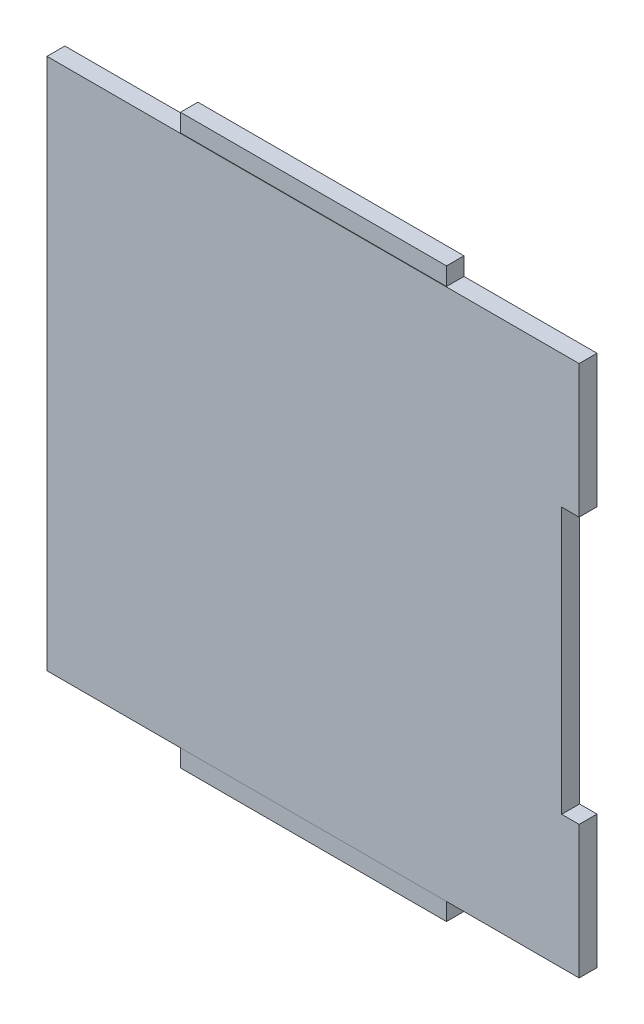
SolidWorks part; units mm, degrees
ref_plane "Front Plane" through (0, 0, 0) normal (0, 0, 1) x (1, 0, 0)
ref_plane "Top Plane" through (0, 0, 0) normal (0, 1, 0) x (1, 0, 0)
ref_plane "Right Plane" through (0, 0, 0) normal (1, 0, 0) x (0, 0, -1)
sketch "Sketch1" plane through (0, 0, 0) normal (0, 0, 1) x (1, 0, 0)
  line L1 (-50, 50) -> (50, 50)
  line L2 (-50, 50) -> (-50, -50)
  line L3 (-50, -50) -> (50, -50)
  line L4 (50, 50) -> (50, -50)
  line L5 (-50, 50) -> (50, -50) construction
  line L6 (-50, -50) -> (50, 50) construction
  point P0 (0, 0)
  dimension "D1" = 100
  dimension "D2" = 100
extrude "Boss-Extrude1" add sketch "Sketch1" along normal blind 3.36
sketch "Sketch2" [suppressed] plane through (0, 0, 3.36) normal (0, 0, 1) x (1, 0, 0)
  line L0 (50, 50) -> (-50, 50) construction
  line L1 (-25, 50) -> (25, 50)
  line L2 (-25, 50) -> (-25, 53.36)
  line L3 (-25, 53.36) -> (25, 53.36)
  line L4 (25, 50) -> (25, 53.36)
  line L5 (0, 0) -> (0, 53.36) construction
  line L6 (0, 0) -> (50, 0) construction
  line L7 (50, -50) -> (50, 50) construction
  dimension "D1" = 3.36
  dimension "D2" = 50
extrude "Boss-Extrude2" [suppressed] add sketch "Sketch2" against normal up to vertex up to point (-50, 50, 0)
mirror "Mirror1" [suppressed] about plane through (0, 0, 0) normal (0, 1, 0)
sketch "Sketch5" [suppressed] plane through (0, 0, 0) normal (0, 0, -1) x (-1, 0, 0)
  line L0 (0, 0) -> (-50, 0) construction
  line L1 (-50, -50) -> (-50, 50) construction
  line L2 (0, 0) -> (0, 53.36) construction
  line L3 (-25, 53.36) -> (25, 53.36) construction
  line L9 (-50, 25) -> (-53.36, 25)
  line L10 (-50, 25) -> (-50, -25)
  line L11 (-50, -25) -> (-53.36, -25)
  line L12 (-53.36, 25) -> (-53.36, -25)
  dimension "D1" = 6.0252
  dimension "D2" = 40.5386
extrude "Boss-Extrude3" [suppressed] add sketch "Sketch5" against normal blind 3.36
mirror "Mirror3" [suppressed] about plane through (0, 0, 0) normal (1, 0, 0)
sketch "Sketch6" plane through (0, 0, 0) normal (0, 0, -1) x (-1, 0, 0)
  line L0 (0, 0) -> (0, -50) construction
  line L1 (50, -50) -> (-50, -50) construction
  line L2 (-50, 0) -> (0, 0) construction
  line L3 (-50, -50) -> (-50, 50) construction
  line L5 (-50, 25) -> (-46.72, 25)
  line L6 (-50, 25) -> (-50, -25)
  line L7 (-50, -25) -> (-46.72, -25)
  line L8 (-46.72, 25) -> (-46.72, -25)
  dimension "D1" = 3.28
  dimension "D2" = 50
extrude "Cut-Extrude1" cut sketch "Sketch6" against normal blind 3.36
sketch "Sketch8" plane through (0, 0, 0) normal (0, 0, -1) x (-1, 0, 0)
  line L0 (0, 0) -> (0, 50) construction
  line L1 (-50, 50) -> (50, 50) construction
  line L2 (0, 0) -> (50, 0) construction
  line L3 (50, 50) -> (50, -50) construction
  line L5 (-25, 50) -> (25, 50)
  line L6 (-25, 50) -> (-25, 53.36)
  line L7 (-25, 53.36) -> (25, 53.36)
  line L8 (25, 50) -> (25, 53.36)
  dimension "D1" = 50
  dimension "D2" = 3.36
extrude "Boss-Extrude4" add sketch "Sketch8" against normal blind 3.28
mirror "Mirror4" about plane through (0, 0, 0) normal (0, 1, 0) of "Boss-Extrude4"
equation "\"Sheet Thickness\"= 3.36mm"
equation "\"Height\"= 100mm"
equation "\"Length\"= 100mm"
equation "\"Width\"= 100mm"
equation "\"D1@Boss-Extrude1\"=\"Sheet Thickness\""
equation "\"D1@Sketch2\"=\"Sheet Thickness\""
equation "\"D2@Sketch2\"=\"Height\"/2"
equation "\"Kerf\"= .08mm"
